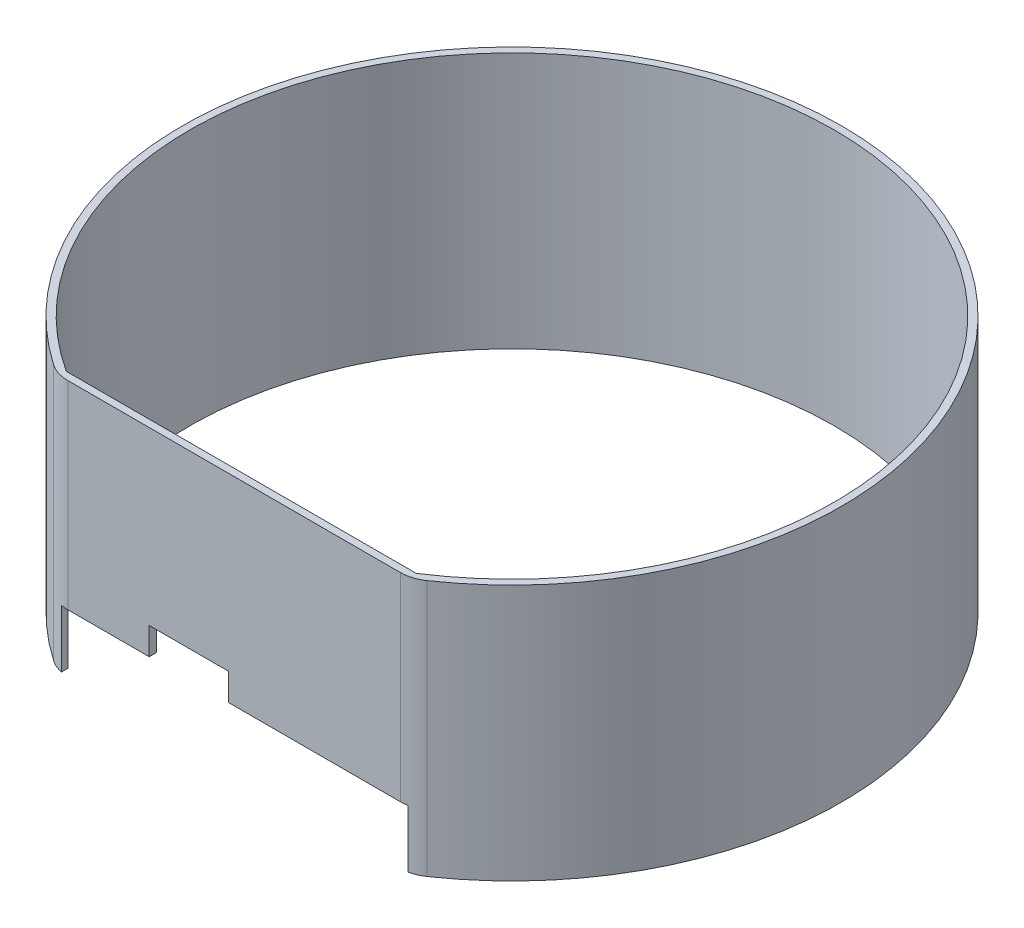
SolidWorks part; units mm, degrees
ref_plane "Front Plane" through (0, 0, 0) normal (0, 0, 1) x (1, 0, 0)
ref_plane "Top Plane" through (0, 0, 0) normal (0, 1, 0) x (1, 0, 0)
ref_plane "Right Plane" through (0, 0, 0) normal (1, 0, 0) x (0, 0, -1)
sketch "Sketch1" plane through (0, 0, 0) normal (0, 1, 0) x (1, 0, 0)
  line L0 (0, 124.168) -> (0, -125.7458) construction
  line L1 (-136.0011, 0) -> (148.623, 0) construction
  line L2 (-48.4715, -75) -> (48.4715, -75)
  line L3 (-49.058, -77) -> (49.058, -77)
  arc A0 (48.4715, -75) -> (-48.4715, -75) centre (0, 0) ccw
  arc A1 (49.058, -77) -> (-49.058, -77) centre (0, 0) ccw
  dimension "D1" = 178.6
  dimension "D3" = 182.6
  dimension "D2" = 75
  dimension "D4" = 77
extrude "Boss-Extrude1" add sketch "Sketch1" along normal blind 71
fillet "Fillet1" radius 10 2 edges at (-49.058, 35.5, 77) (49.058, 35.5, 77)
sketch "Sketch2" plane through (0, 0, 77) normal (0, 0, 1) x (1, 0, 0)
  line L0 (0, 94.4811) -> (0, -36.6428) construction
  line L1 (46.051, 0) -> (51.7153, 0) construction
  line L2 (-48, 16) -> (48, 16)
  line L4 (-48, 16) -> (-48, 0)
  line L5 (-48, 0) -> (48, 0)
  line L6 (48, 16) -> (48, 0)
  line L7 (-48, 16) -> (48, 0) construction
  line L8 (-48, 0) -> (48, 16) construction
  line L9 (-46.051, 71) -> (46.051, 71) construction
  point P3 (0, 8)
  dimension "D1" = 55
  dimension "D2" = 96
extrude "Cut-Extrude1" cut sketch "Sketch2" against normal blind 5
sketch "Sketch3" plane through (0, 0, 77) normal (0, 0, 1) x (1, 0, 0)
  line L0 (0, 94.4811) -> (0, -26.607) construction
  line L1 (46.051, 16) -> (-46.051, 16) construction
  line L2 (-23.5, 16) -> (-1.5, 16)
  line L3 (-23.5, 16) -> (-23.5, 23.5)
  line L4 (-23.5, 23.5) -> (-1.5, 23.5)
  line L5 (-1.5, 16) -> (-1.5, 23.5)
  dimension "D1" = 22
  dimension "D2" = 7.5
  dimension "D3" = 1.5
extrude "Cut-Extrude2" cut sketch "Sketch3" against normal blind 5
equation "\"D5@Sketch4\"=20-\"D2@Sketch4\"-2"
equation "\"D9@Sketch5\"=20-\"D6@Sketch5\"-2"
